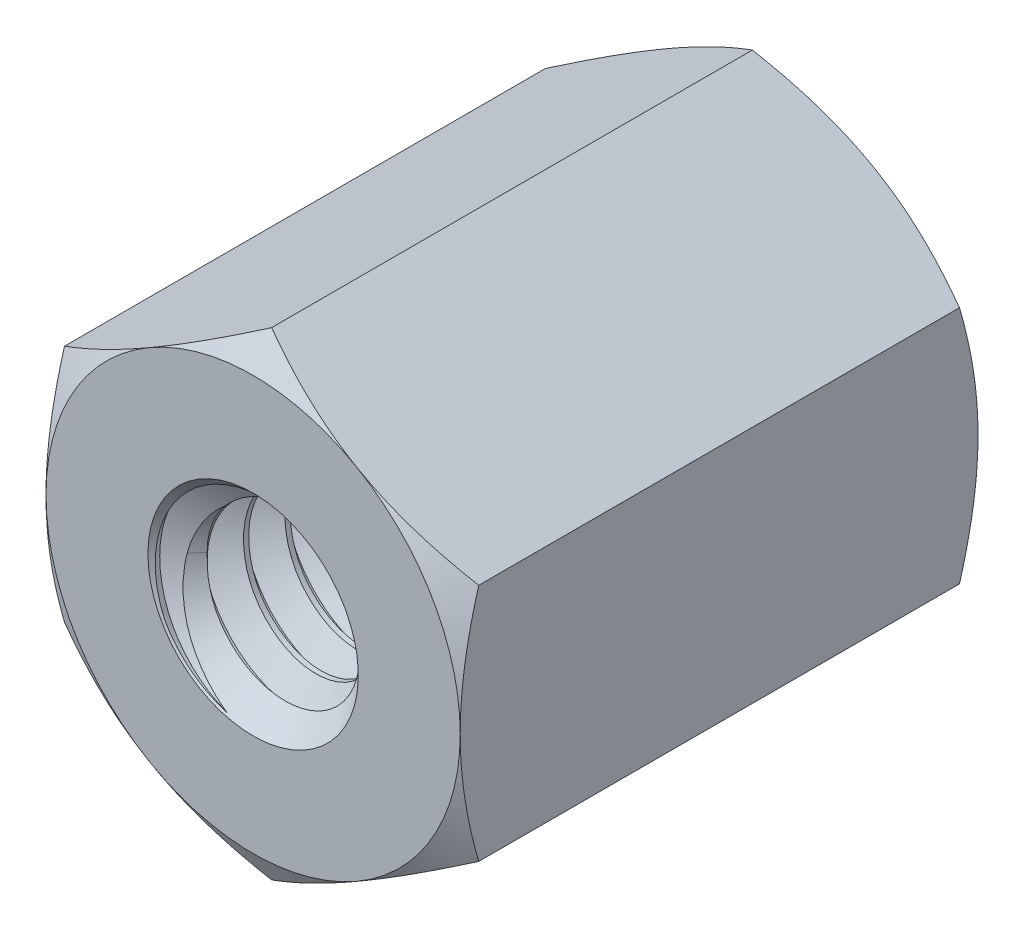
SolidWorks part; units mm, degrees
ref_plane "Front Plane" through (0, 0, 0) normal (0, 0, 1) x (1, 0, 0)
ref_plane "Top Plane" through (0, 0, 0) normal (0, 1, 0) x (1, 0, 0)
ref_plane "Right Plane" through (0, 0, 0) normal (1, 0, 0) x (0, 0, -1)
sketch "Sketch3" plane through (0, 0, 0) normal (1, 0, 0) x (0, 0, -1)
  line L0 (-7.9375, 0) -> (7.9375, 0) construction
  line L1 (0, 6.35) -> (0, -6.35) construction
  line L2 (-7.9375, 3.175) -> (-7.9375, -3.175) construction
  point P2 (-7.9375, 0)
  point P3 (7.9375, 0)
  dimension "Length" = 15.875
  dimension "Min Thread Length" = 15.875
  dimension "D1" = 15.875
  dimension "Thread Dia" = 6.35
  dimension "Hex" = 12.7
sketch "Sketch1" plane through (0, 0, 0) normal (0, 0, 1) x (1, 0, 0)
  line L1 (0, 7.3323) -> (-6.35, 3.6662)
  line L2 (-6.35, 3.6662) -> (-6.35, -3.6662)
  line L3 (-6.35, -3.6662) -> (0, -7.3323)
  line L4 (0, -7.3323) -> (6.35, -3.6662)
  line L5 (6.35, -3.6662) -> (6.35, 3.6662)
  line L6 (6.35, 3.6662) -> (0, 7.3323)
  circle A0 centre (0, 0) radius 6.35 construction
  circle A1 centre (0, 0) radius 3.175
extrude "Extrude1" add sketch "Sketch1" along normal up to vertex (7.9375 mm away) and the other way up to vertex (7.9375 mm away) up to point (0, 0, 7.9375) other way up to point (0, 0, -7.9375)
sketch "Sketch11" plane through (0, 0, -7.9375) normal (0, 0, -1) x (-1, 0, 0)
  circle A0 centre (0, 0) radius 3.175 construction
  circle A1 centre (0, 0) radius 3.175
curve "Helix/Spiral1" pitch 1.27 height 17.145 radius 3.175 centre (0, 0, -7.9375) axis (0, 0, 1) start towards (0, 1, 0) parameters "Pitch"=1.27
sketch "Sketch12" plane through (0, 0, 0) normal (1, 0, 0) x (0, 0, -1)
  line L0 (9.0488, 3.175) -> (7.9375, 3.175)
  line L1 (9.0488, 3.175) -> (8.5725, 2.3501)
  line L2 (8.5725, 2.3501) -> (8.4138, 2.3501)
  line L3 (8.4138, 2.3501) -> (7.9375, 3.175)
  line L4 (8.4931, 2.3501) -> (8.4931, 3.175) construction
  line L5 (8.8106, 2.7626) -> (8.1756, 2.7626) construction
  dimension "D1" = 0.1588
  dimension "D2" = 0.635
  dimension "D3" = 60
sweep "Sweep1" add profiles "Sketch12" path "Helix/Spiral1"
sketch "Sketch6" plane through (0, 0, -7.9375) normal (0, 0, -1) x (-1, 0, 0)
  line L6 (0, 7.3323) -> (-6.35, 3.6662)
  line L7 (-6.35, 3.6662) -> (-6.35, -3.6662)
  line L8 (-6.35, -3.6662) -> (0, -7.3323)
  line L9 (0, -7.3323) -> (6.35, -3.6662)
  line L10 (6.35, -3.6662) -> (6.35, 3.6662)
  line L11 (6.35, 3.6662) -> (0, 7.3323)
  line L12 (0, 7.3323) -> (-6.35, 3.6662)
  line L13 (-6.35, 3.6662) -> (-6.35, -3.6662)
  line L14 (-6.35, -3.6662) -> (0, -7.3323)
  line L15 (0, -7.3323) -> (6.35, -3.6662)
  line L16 (6.35, -3.6662) -> (6.35, 3.6662)
  line L17 (6.35, 3.6662) -> (0, 7.3323)
  dimension "D1" = 0
extrude "Extrude2" cut sketch "Sketch6" along normal through all
sketch "Sketch7" plane through (0, 0, -7.9375) normal (0, 0, -1) x (-1, 0, 0)
  circle A2 centre (0, 0) radius 3.2258
  circle A3 centre (0, 0) radius 3.2258
  dimension "D1" = 0.0508
extrude "Extrude3" cut sketch "Sketch7" against normal through all draft 43
sketch "Sketch8" plane through (0, 0, -7.9375) normal (0, 0, -1) x (-1, 0, 0)
  circle A0 centre (0, 0) radius 6.35 construction
  circle A1 centre (0, 0) radius 6.35
extrude "Extrude4" cut sketch "Sketch8" against normal through all draft 60 flip side to cut
mirror "Mirror1" about plane through (0, 0, 0) normal (0, 0, 1) of "Extrude2", "Extrude3", "Extrude4"
sketch "Sketch9" [suppressed] plane through (0, 0, 0) normal (1, 0, 0) x (0, 0, -1)
  line L1 (-22.225, 3.2258) -> (22.225, 3.2258)
  line L2 (-22.225, 3.2258) -> (-22.225, 0)
  line L3 (-22.225, 0) -> (22.225, 0)
  line L4 (22.225, 3.2258) -> (22.225, 0)
  line L7 (-38.1, 0) -> (38.1, 0) construction
revolve "Revolve" [suppressed] add sketch "Sketch9" angle 360 about L0
sketch "Sketch10" [suppressed] plane through (0, 0, 0) normal (1, 0, 0) x (0, 0, -1)
  line L0 (38.1, 3.175) -> (22.225, 3.175)
  line L1 (-38.1, 3.175) -> (-22.225, 3.175)
  line L2 (22.225, 3.175) -> (22.225, -3.175)
  line L3 (-38.1, -3.2258) -> (-22.225, -3.2258)
  line L4 (-22.225, 3.175) -> (-22.225, -3.2258)
  line L5 (22.225, -3.175) -> (38.1, -3.175)
equation "\"D1@Sketch3\" = \"Min Thread Length@Sketch3\""
equation "\"D3@Helix/Spiral1\" = \"Length@Sketch3\"+\"Pitch@Helix/Spiral1\""
equation "\"D1@Sketch12\" = \"Pitch@Helix/Spiral1\"*.125"
equation "\"D2@Sketch12\" = \"Pitch@Helix/Spiral1\"*.5"
